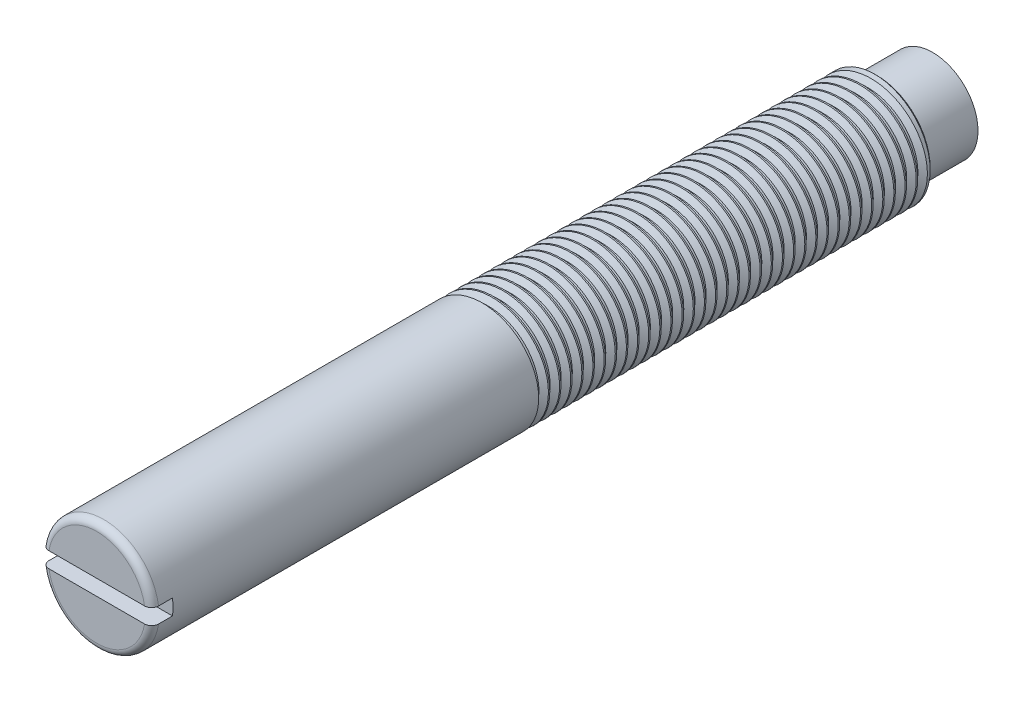
SolidWorks part; units mm, degrees
material "SAE X-1315 Steel"
ref_plane "Front Plane" through (0, 0, 0) normal (0, 0, 1) x (1, 0, 0)
ref_plane "Top Plane" through (0, 0, 0) normal (0, 1, 0) x (1, 0, 0)
ref_plane "Right Plane" through (0, 0, 0) normal (1, 0, 0) x (0, 0, -1)
sketch "Sketch3" plane through (0, 0, 0) normal (1, 0, 0) x (0, 0, -1)
  line L0 (-32.0982, 0) -> (42951.8564, 0) construction
  line L2 (-64.3533, 0) -> (-64.3533, 6.3119)
  line L3 (-64.3533, 6.3119) -> (24.5467, 6.3119)
  line L4 (24.5467, 6.3119) -> (24.5467, 5.1594)
  line L5 (24.5467, 5.1594) -> (30.8967, 5.1594)
  line L6 (30.8967, 5.1594) -> (30.8967, 0)
  line L7 (-64.3533, 0) -> (30.8967, 0)
  dimension "D1" = 95.25
  dimension "D2" = 10.3187
  dimension "D3" = 6.35
  dimension "D4" = 12.6238
revolve "Revolve1" add sketch "Sketch3" angle 360 about L7
sketch "Sketch4" plane through (0, 0, 64.3533) normal (0, 0, 1) x (1, 0, 0)
  line L0 (-2.8756, 0) -> (49997.1244, 0) construction
  line L3 (-12.4306, 0.889) -> (11.9113, 0.889)
  line L4 (-12.4306, 0.889) -> (-12.4306, -0.889)
  line L5 (-12.4306, -0.889) -> (11.9113, -0.889)
  line L6 (11.9113, 0.889) -> (11.9113, -0.889)
  dimension "D1" = 1.778
extrude "Cut-Extrude1" cut sketch "Sketch4" against normal blind 2.3813 contours L3 L6 L5 L4
fillet "Fillet1" radius 0.7937 2 edges at (0, -6.3119, 64.3533) (0, 6.3119, 64.3533)
ref_plane "Plane2" through (0, 0, 64.3533) normal (0, 0, 1) x (1, 0, 0)
ref_plane "Plane3" through (0, 0, 19.9033) normal (0, 0, 1) x (1, 0, 0)
chamfer "Chamfer1" distance 0.254 angle 45 1 edges at (6.3119, 0, -24.5467)
thread "Thread1" pitch 1.27 method cut profile "Thread Profile1" start angle 270, offset 0, length 44.45, pitch 1.27, diameter 12.6238
ref_plane "Plane4" through (0, -6.3119, -24.2927) normal (-1, 0, 0) x (0, -1, 0)
sketch "Thread Profile1" plane through (0, -6.3119, -24.2927) normal (-1, 0, 0) x (0, -1, 0)
  line L0 (0, 0) -> (0, 1.27) construction
  line L11 (0, 0) -> (0, 1.1112)
  line L12 (0, 1.1112) -> (-0.6874, 0.7144)
  line L13 (-0.6874, 0.7144) -> (-0.6874, 0.3969)
  line L15 (-0.6874, 0.3969) -> (0, 0)
  line L17 (-0.6874, 0.5556) -> (0, 0.5556) construction
  point P2 (0, 0)
  dimension "Pitch" = 1.27
  dimension "Profile_Angle" = 60
  dimension "Profile_Land" = 0.3175
  dimension "Profile_Height" = 0.6874
